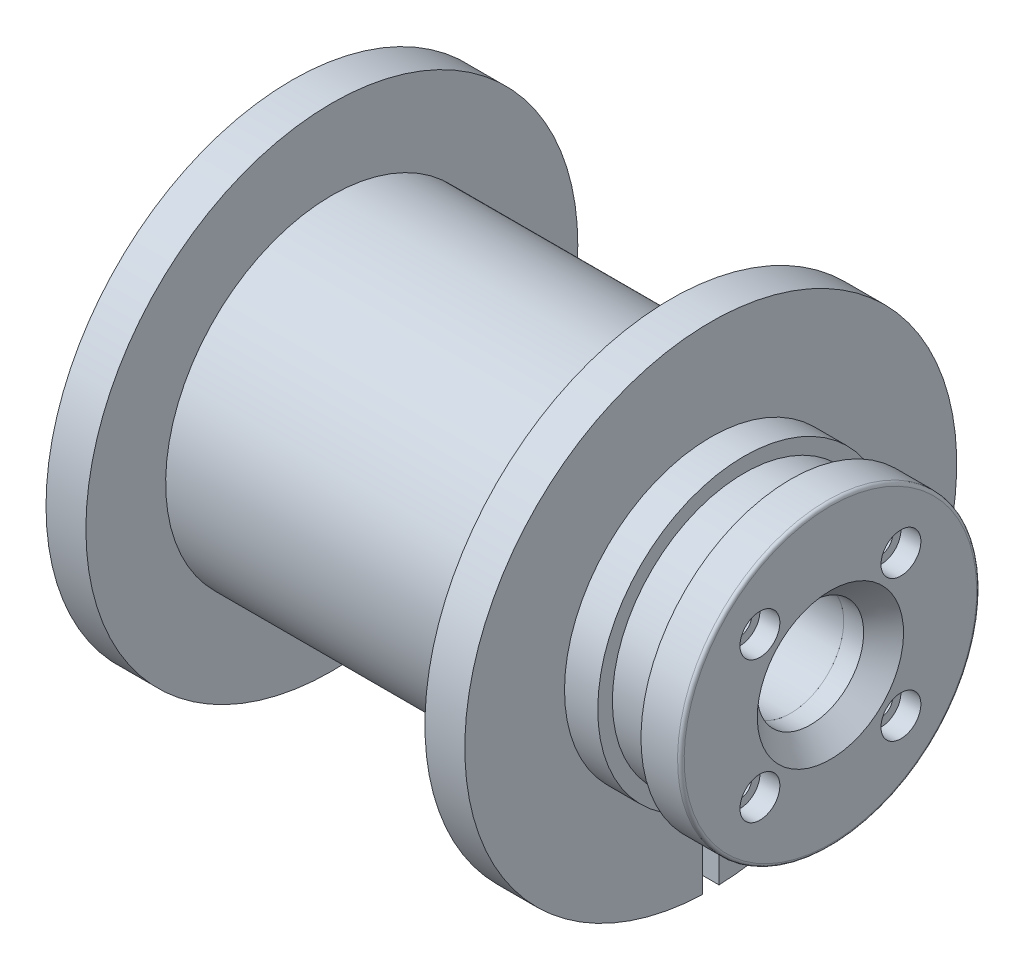
SolidWorks part; units mm, degrees
material "ABS"
ref_plane "正面" through (0, 0, 0) normal (0, 0, 1) x (1, 0, 0)
ref_plane "平面" through (0, 0, 0) normal (0, 1, 0) x (1, 0, 0)
ref_plane "右側面" through (0, 0, 0) normal (1, 0, 0) x (0, 0, -1)
sketch "元ライン_平面" plane through (0, 0, 0) normal (0, 1, 0) x (1, 0, 0)
  line L4 (0.4585, 2.4585) -> (0.4585, -2.4585) construction
  point P0 (0, 0)
  line B0 (31, -40) -> (41, -40)
  line B1 (41, -40) -> (41, 40)
  line B2 (41, 40) -> (31, 40)
  line B3 (31, 40) -> (31, -40)
  line B4 (-42, 79) -> (-130, 79)
  line B5 (-130, 79) -> (-133, 76)
  line B6 (-133, 76) -> (-133, -76)
  line B7 (-133, -76) -> (-130, -79)
  line B8 (-130, -79) -> (-42, -79)
  line B9 (-42, -79) -> (-39, -76)
  line B10 (-39, -76) -> (-39, -40)
  line B11 (-39, -40) -> (31, -40)
  line B12 (31, -40) -> (31, 40)
  line B13 (31, 40) -> (-39, 40)
  line B14 (-39, 40) -> (-39, 76)
  line B15 (-39, 76) -> (-42, 79)
  line B16 (-39, 41.9) -> (-39, -41.9)
  line B17 (43, 38) -> (41, 40)
  line B18 (43, -37.6198) -> (43, 37.6198)
  line B19 (41, -40) -> (43, -38)
  line B20 (-34, -11) -> (1, -11)
  line B21 (-44, -12.5) -> (-34, -12.5)
  line B22 (-34, -12.5) -> (-34, 12.5)
  line B23 (-34, 12.5) -> (-44, 12.5)
  line B24 (1, 11) -> (-34, 11)
  line B25 (1, -11) -> (1, 11)
  line B26 (-13.4, -2.4585) -> (0.4585, -2.4585)
  line B27 (0.4585, 2.4585) -> (-13.4, 2.4585)
  line B28 (-13.4, -2.4585) -> (-13.4, 2.4585)
  line B29 (-28, -3) -> (1, -3)
  line B30 (1, 3) -> (-28, 3)
  arc B31 (-28, 3) -> (-28, -3) centre (-28, 0) ccw
  line B32 (34, 40) -> (34, -40) construction
  line B33 (-34, 0) -> (34, 0) construction
  dimension "D1" = 4.917
sketch_block_instance "ﾌﾞﾛｯｸ1-1"
sketch_block "ﾌﾞﾛｯｸ1" parameters "D1"=3
ref_plane "平面1" through (-34, 0, 0) normal (1, 0, 0) x (0, 0, -1)
ref_plane "平面2" through (34, 0, 0) normal (1, 0, 0) x (0, 0, -1)
sketch "元ライン_側面1" plane through (-34, 0, 0) normal (1, 0, 0) x (0, 0, -1)
  line L0 (-12.5, 0) -> (12.5, 0) construction
  circle A1 centre (0, 0) radius 11 construction
  circle A2 centre (0, 0) radius 2.4585
  line B0 (-3, 13.5) -> (-3, 10.583)
  line B1 (3, 10.583) -> (3, 13.5)
  line B2 (3, 13.5) -> (-3, 13.5)
  line B3 (-52, 22.4) -> (-52, -87)
  line B4 (-52, -87) -> (52, -87)
  line B5 (52, -87) -> (52, 22.4)
  line B6 (41.9, 32.5) -> (-41.9, 32.5)
  arc B7 (-3, 10.583) -> (3, 10.583) centre (0, 0) ccw
  circle B8 centre (0, 0) radius 2.4585
  circle B9 centre (0, -20) radius 45.5
  arc B10 (52, 22.4) -> (41.9, 32.5) centre (41.9, 22.4) ccw
  arc B11 (-41.9, 32.5) -> (-52, 22.4) centre (-41.9, 22.4) ccw
  dimension "D1" = 22
  dimension "D2" = 4.917
sketch_block_instance "ﾌﾞﾛｯｸ2-1"
sketch_block "ﾌﾞﾛｯｸ2"
sketch "元ライン_側面2" plane through (34, 0, 0) normal (1, 0, 0) x (0, 0, -1)
  line B0 (-38, -105) -> (38, -105)
  line B1 (-40, -103) -> (-38, -105)
  line B2 (-40, 0) -> (-40, -103)
  line B3 (40, -103) -> (40, 0)
  line B4 (38, -105) -> (40, -103)
  circle B5 centre (0, 0) radius 24
  circle B6 centre (30, -99) radius 3.1
  circle B7 centre (-30, -99) radius 3.1
  circle B8 centre (0, 32) radius 1.5
  circle B9 centre (27.7128, -16) radius 1.5
  circle B10 centre (27.7128, 16) radius 1.5
  circle B11 centre (0, -32) radius 1.5
  circle B12 centre (-27.7128, -16) radius 1.5
  circle B13 centre (-27.7128, 16) radius 1.5
  circle B14 centre (-20, -99) radius 1.5
  circle B15 centre (20, -99) radius 1.5
  arc B16 (40, 0) -> (-40, 0) centre (0, 0) ccw
sketch_block_instance "ﾌﾞﾛｯｸ3-1"
sketch_block "ﾌﾞﾛｯｸ3"
sketch "ｽｹｯﾁ4" plane through (0, 0, 0) normal (0, 0, 1) x (1, 0, 0)
  line L0 (0, 25) -> (0, -17.4515) construction
  line L1 (-34, 11.2) -> (-34, 37)
  line L2 (-34, 37) -> (-28, 37)
  line L3 (-28, 37) -> (-28, 25)
  line L4 (-28, 25) -> (23, 25)
  line L5 (23, 37) -> (23, 25)
  line L6 (29, 37) -> (23, 37)
  line L7 (41, 8) -> (41, 19.8)
  line L8 (-34, 0) -> (34, 0) construction
  line L9 (-34, 0) -> (41, 0) construction
  line L10 (29, 37) -> (29, 22)
  line L11 (34, 19.8) -> (41, 19.8)
  line L12 (29, 22) -> (34, 22)
  line L13 (-34, 11.2) -> (1, 11.2)
  line L14 (1, 11.2) -> (1, 3.2)
  line L15 (1, 3.2) -> (11, 3.2)
  line L16 (11, 3.2) -> (11, 8)
  line L17 (11, 8) -> (41, 8)
  line L18 (34, 22) -> (34, 19.8)
  line L19 (41, 40) -> (31, 40) construction
  line L20 (41, 40) -> (31, 40) construction
  line L21 (-34, 11) -> (1, 11) construction
  point P2 (31, 0)
  point P10 (43, 0)
  point P12 (34, 0)
  point P16 (-13.4, 0)
  point P19 (0.4585, 0)
  dimension "D1" = 12
  dimension "D2" = 25
  dimension "D3" = 51
  dimension "D4" = 2
  dimension "D5" = 6
  dimension "D6" = 0
  dimension "D7" = 6
  dimension "D8" = 3.2
  dimension "D9" = 10
  dimension "D10" = 8
  dimension "D11" = 2
  dimension "D12" = 19.8
  dimension "D13" = 22
  dimension "D14" = 3
  dimension "D15" = 0.2
revolve "回転1" add sketch "ｽｹｯﾁ4" angle 360 about L9
sketch "ｽｹｯﾁ5" plane through (-34, 0, 0) normal (-1, 0, 0) x (0, 0, 1)
  line L0 (-11, -11) -> (11, -11) construction
  line L1 (-3, 13.5) -> (3, 13.5)
  line L2 (-3, 13.5) -> (-3, 7.5)
  line L3 (-3, 7.5) -> (3, 7.5)
  line L4 (3, 13.5) -> (3, 7.5)
  line L5 (-11, 0) -> (11, 0) construction
  circle A0 centre (0, 0) radius 11 construction
  point P4 (0, 7.5)
  point P15 (0, -11)
  dimension "D2" = 22
  dimension "D1" = 6
  dimension "D3" = 18.5
  dimension "D4" = 24.5
extrude "ｶｯﾄ - 押し出し3" cut sketch "ｽｹｯﾁ5" against normal up to surface (35 mm away) up to face at (1, -3.2, 0)
sketch "ｽｹｯﾁ7" plane through (41, 0, 0) normal (-1, 0, 0) x (0, 0, 1)
  line L1 (0, -11.2) -> (0, -25) construction
  line L3 (-1.25, -22.4229) -> (-1.25, -36.9789)
  line L5 (1.25, -22.4229) -> (1.25, -36.9789)
  circle A0 centre (0, -18.1) radius 4.5
  arc A1 (-1.25, -36.9789) -> (1.25, -36.9789) centre (0, 0) ccw
  arc A3 (-3, 10.7907) -> (3, 10.7907) centre (0, 0) ccw construction
  circle A4 centre (0, 0) radius 25 construction
  circle A5 centre (0, 0) radius 37 construction
  point P17 (0, -18.1)
  circle M18 centre (0, 0) radius 19.8
  dimension "D1" = 9
  dimension "D2" = 2.5
extrude "ピン穴" cut sketch "ｽｹｯﾁ7" along normal up to surface (69 mm away) contours A0 L1 M18 | L1 A0 M18 | L1 A0 M18 | L1 A0 M18 | A1 L3 A0 region at (41, -16.994, 1.9672) region at (41, -16.994, -1.9672) region at (41, -20.8634, 1.7666) region at (41, -20.8634, -1.7666) region at (41, -29.7671, 0) up to face at (-28, -37, 0)
sketch "ｽｹｯﾁ11" plane through (41, 0, 0) normal (1, 0, 0) x (0, 0, -1)
  line L1 (-10.6066, 10.6066) -> (10.6066, 10.6066) construction
  line L2 (-10.6066, 10.6066) -> (-10.6066, -10.6066) construction
  line L3 (-10.6066, -10.6066) -> (10.6066, -10.6066) construction
  line L4 (10.6066, 10.6066) -> (10.6066, -10.6066) construction
  circle A0 centre (-10.6066, 10.6066) radius 1.1
  circle A1 centre (-10.6066, -10.6066) radius 1.1
  circle A2 centre (10.6066, 10.6066) radius 1.1
  circle A3 centre (10.6066, -10.6066) radius 1.1
  circle A4 centre (-10.6066, 10.6066) radius 3 construction
  point P4 (-10.6066, 0)
  point P6 (0, 10.6066)
  dimension "D2" = 2.2
  dimension "D3" = 6
  dimension "D1" = 30
extrude "ｶｯﾄ - 押し出し8" cut sketch "ｽｹｯﾁ11" against normal blind 20
sketch "ｽｹｯﾁ12" plane through (41, 0, 0) normal (1, 0, 0) x (0, 0, -1)
  circle A0 centre (0, 0) radius 22.5
  circle A1 centre (0, 0) radius 8 construction
  circle A2 centre (0, 0) radius 8
  circle A3 centre (-10.6066, 10.6066) radius 1.75
  circle A4 centre (10.6066, 10.6066) radius 1.75
  circle A5 centre (10.6066, -10.6066) radius 1.75
  circle A6 centre (-10.6066, -10.6066) radius 1.75
  dimension "D1" = 45
  dimension "D2" = 3.5
extrude "ﾎﾞｽ - 押し出し1" add sketch "ｽｹｯﾁ12" along normal blind 3 separate body
sketch "ｽｹｯﾁ13" plane through (44, 0, 0) normal (1, 0, 0) x (0, 0, -1)
  circle A0 centre (-10.6066, 10.6066) radius 3
  circle A1 centre (-10.6066, -10.6066) radius 3
  circle A2 centre (10.6066, 10.6066) radius 3
  circle A3 centre (10.6066, -10.6066) radius 3
  circle A4 centre (0, 0) radius 8 construction
  circle A5 centre (0, 0) radius 22.5
  circle A6 centre (0, 0) radius 22.5
  circle A7 centre (0, 0) radius 8
  dimension "D1" = 6
  dimension "D2" = 0
extrude "ﾎﾞｽ - 押し出し2" add sketch "ｽｹｯﾁ13" along normal blind 3
fillet "ﾌｨﾚｯﾄ1" radius 0.5 1 edges at (47, 22.5, 0)
chamfer "面取り1" distance 3 angle 45 1 edges at (47, 8, 0)
fillet "ﾌｨﾚｯﾄ2" radius 0.5 1 edges at (11, -8, 0)
